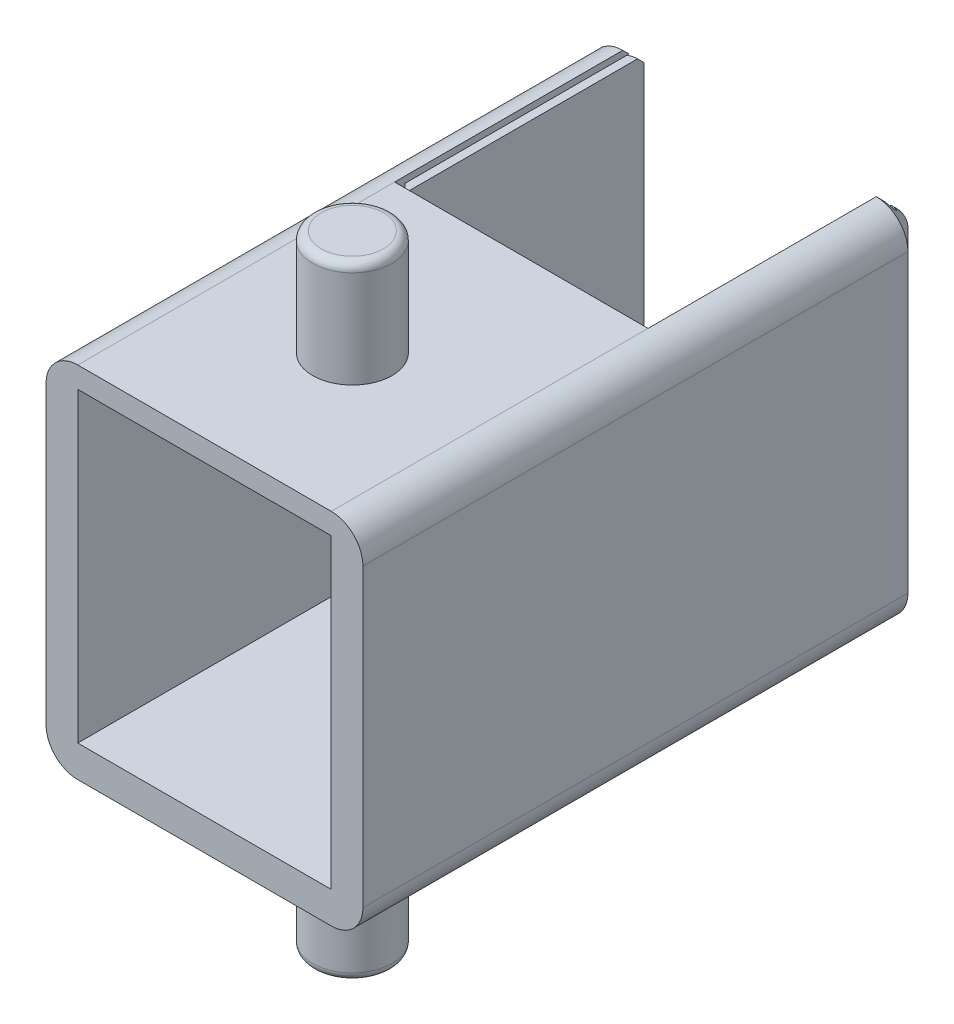
SolidWorks part; units mm, degrees
ref_plane "Front Plane" through (0, 0, 0) normal (0, 0, 1) x (1, 0, 0)
ref_plane "Top Plane" through (0, 0, 0) normal (0, 1, 0) x (1, 0, 0)
ref_plane "Right Plane" through (0, 0, 0) normal (1, 0, 0) x (0, 0, -1)
sketch "Sketch1" plane through (0, 0, 0) normal (0, 0, 1) x (1, 0, 0)
  line L1 (15.24, -19.685) -> (-15.24, -19.685)
  line L4 (-15.24, -19.685) -> (-15.24, 19.685)
  line L5 (15.24, -19.685) -> (-15.24, 19.685) construction
  line L6 (15.24, 19.685) -> (-15.24, -19.685) construction
  line L7 (-15.24, 19.685) -> (-19.05, 19.685)
  line L8 (-19.05, 19.685) -> (-19.05, -23.495)
  line L9 (-19.05, -23.495) -> (15.24, -23.495)
  line L11 (15.24, -19.685) -> (15.24, 19.685)
  line L12 (19.05, 19.685) -> (19.05, -23.495)
  line L13 (19.05, -23.495) -> (15.24, -23.495)
  line L16 (19.05, 19.685) -> (15.24, 19.685)
  point P0 (0, 0)
  point P8 (-15.24, 0)
  point P11 (-19.05, -1.905)
  point P13 (0, -19.685)
  dimension "D1" = 39.37
  dimension "D2" = 30.48
  dimension "D4" = 3.81
  dimension "D5" = 3.81
  dimension "D6" = 3.81
extrude "Boss-Extrude1" add sketch "Sketch1" along normal blind 69.85
sketch "Sketch2" plane through (0, 19.685, 0) normal (0, 1, 0) x (1, 0, 0)
  line L0 (-15.24, 0) -> (-19.05, 0) construction
  line L1 (-19.05, 0) -> (19.05, 0)
  line L2 (19.05, -69.85) -> (19.05, 0) construction
  line L3 (19.05, 0) -> (15.24, 0) construction
  arc A0 (-19.05, 0) -> (19.05, 0) centre (0, 70.1675) ccw
  point P7 (0, -2.54)
  dimension "D1" = 2.54
extrude "Cut-Extrude1" cut sketch "Sketch2" against normal blind 50.8
sketch "Sketch3" plane through (0, 19.685, 0) normal (0, 1, 0) x (1, 0, 0)
  line L1 (11.176, -28.194) -> (-11.176, -28.194) construction
  line L2 (11.176, -28.194) -> (11.176, -5.842) construction
  line L3 (11.176, -5.842) -> (-11.176, -5.842) construction
  line L4 (-11.176, -28.194) -> (-11.176, -5.842) construction
  line L5 (11.176, -28.194) -> (-11.176, -5.842) construction
  line L6 (11.176, -5.842) -> (-11.176, -28.194) construction
  circle A0 centre (-11.176, -5.842) radius 1.27
  circle A1 centre (11.176, -5.842) radius 1.27
  circle A2 centre (11.176, -28.194) radius 1.27
  circle A3 centre (-11.176, -28.194) radius 1.27
  circle A4 centre (0, -17.018) radius 3.81
  point P0 (0, -17.018)
  dimension "D3" = 2.54
  dimension "D4" = 7.62
  dimension "D1" = 22.352
  dimension "D2" = 5.842
extrude "Cut-Extrude2" cut sketch "Sketch3" against normal blind 50.8
sketch "Sketch4" plane through (0, 19.685, 0) normal (0, 1, 0) x (1, 0, 0)
  line L0 (15.24, -69.85) -> (15.24, -0.9249) construction
  line L1 (-15.24, -69.85) -> (15.24, -69.85)
  line L2 (-15.24, -69.85) -> (-15.24, -31.75)
  line L3 (-15.24, -31.75) -> (15.24, -31.75)
  line L4 (15.24, -69.85) -> (15.24, -31.75)
  dimension "D1" = 38.1
extrude "Boss-Extrude2" add sketch "Sketch4" against normal blind 2.54
sketch "Sketch5" plane through (-15.24, 0, 0) normal (1, 0, 0) x (0, 0, -1)
  line L0 (0, -23.495) -> (0, 19.685) construction
  line L1 (0, 17.907) -> (-30.48, 17.907)
  line L2 (0, 17.907) -> (0, 18.923)
  line L3 (0, 18.923) -> (-30.48, 18.923)
  line L4 (-30.48, 17.907) -> (-30.48, 18.923)
  line L5 (-69.85, 19.685) -> (0, 19.685) construction
  dimension "D1" = 30.48
  dimension "D2" = 1.016
  dimension "D3" = 0.762
extrude "Cut-Extrude3" cut sketch "Sketch5" against normal blind 1.016
mirror "Mirror1" about plane through (0, 0, 0) normal (1, 0, 0) of "Cut-Extrude3"
fillet "Fillet1" radius 3.81 4 edges at (19.05, 19.685, 34.925) (19.05, -23.495, 34.925) (-19.05, -23.495, 34.925) (-19.05, 19.685, 34.925)
sketch "Sketch6" plane through (0, 19.685, 0) normal (0, 1, 0) x (1, 0, 0)
  line L1 (15.24, -69.85) -> (-15.24, -69.85) construction
  circle A0 centre (0, -52.07) radius 4.7625
  dimension "D1" = 9.525
  dimension "D2" = 17.78
extrude "Boss-Extrude3" add sketch "Sketch6" along normal blind 12.7
sketch "Sketch8" plane through (0, -23.495, 0) normal (0, -1, 0) x (1, 0, 0)
  circle A0 centre (0, 52.07) radius 4.7625
  circle A1 centre (0, 52.07) radius 4.7625 construction
extrude "Boss-Extrude4" add sketch "Sketch8" along normal blind 19.05
fillet "Fillet2" radius 1.016 2 edges at (0, 32.385, 56.8325) (0, -42.545, 47.3075)
ref_plane "Plane1" through (0, 0, 1.778) normal (0, 0, -1) x (-1, 0, 0)
sketch "Sketch9" plane through (0, 0, 1.778) normal (0, 0, -1) x (-1, 0, 0)
  line L1 (-19.05, 19.685) -> (19.05, 19.685)
  line L2 (-19.05, 19.685) -> (-19.05, -23.495)
  line L3 (-19.05, -23.495) -> (19.05, -23.495)
  line L4 (19.05, 19.685) -> (19.05, -23.495)
extrude "Cut-Extrude4" cut sketch "Sketch9" along direction (0, 0, -1) on the side of the normal blind 2.032 contours L2 L1 L4 L3
chamfer "Chamfer1" distance 2.54 angle 45 7 edges at (-17.9341, 18.5691, 1.778) (-17.9341, -22.3791, 1.778) (-19.05, -1.905, 1.778) (12.8694, -23.495, 1.778) (17.9341, 18.5691, 1.778) (17.9341, -22.3791, 1.778) (19.05, -1.905, 1.778)
